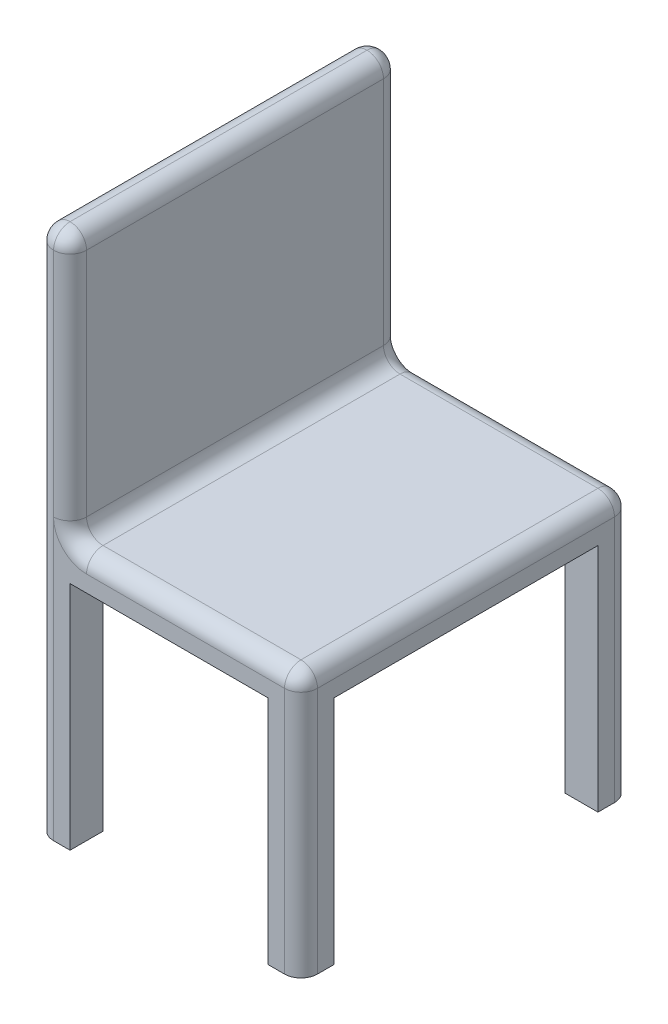
SolidWorks part; units mm, degrees
ref_plane "前基準面" through (0, 0, 0) normal (0, 0, 1) x (1, 0, 0)
ref_plane "上基準面" through (0, 0, 0) normal (0, 1, 0) x (1, 0, 0)
ref_plane "右基準面" through (0, 0, 0) normal (1, 0, 0) x (0, 0, -1)
sketch "草圖1" plane through (0, 0, 0) normal (0, 0, 1) x (1, 0, 0)
  line L0 (0, 0) -> (0, 16)
  line L1 (0, 16) -> (1, 16)
  line L2 (1, 16) -> (1, 8)
  line L3 (1, 8) -> (8, 8)
  line L4 (8, 8) -> (8, 0)
  line L5 (8, 0) -> (7, 0)
  line L6 (7, 0) -> (7, 7)
  line L7 (7, 7) -> (1, 7)
  line L8 (1, 7) -> (1, 0)
  line L9 (1, 0) -> (0, 0)
  point P11 (4.5, 8)
  dimension "D1" = 16
  dimension "D2" = 8
  dimension "D3" = 1
  dimension "D4" = 1
  dimension "D5" = 1
  dimension "D6" = 8
extrude "填料-伸長1" add sketch "草圖1" along normal blind 10
sketch "草圖2" plane through (8, 0, 0) normal (1, 0, 0) x (0, 0, -1)
  line L0 (-10, 0) -> (0, 0) construction
  line L1 (-9, 0) -> (-1, 0)
  line L2 (-9, 0) -> (-9, 7)
  line L3 (-9, 7) -> (-1, 7)
  line L4 (-1, 0) -> (-1, 7)
  line L5 (-10, 0) -> (-10, 8) construction
  line L6 (0, 0) -> (0, 8) construction
  line L7 (-10, 8) -> (0, 8) construction
  dimension "D1" = 1
  dimension "D2" = 1
  dimension "D3" = 1
extrude "除料-伸長1" cut sketch "草圖2" against normal through all
fillet "圓角1" radius 0.5 6 edges at (1, 12, 10) (1, 12, 0) (4.5, 8, 10) (1, 8, 5) (8, 8, 5) (4.5, 8, 0)
fillet "圓角4" radius 0.5 7 edges at (7.8536, 7.8536, 9.8536) (7.8536, 7.8536, 0.1464) (0, 16, 5) (0, 8, 0) (0, 8, 10) (8, 3.75, 10) (8, 3.75, 0)
fillet "圓角5" radius 0.5 5 edges at (0.1464, 15.8536, 9.8536) (0.8536, 16, 9.8536) (1, 16, 5) (0.1464, 15.8536, 0.1464) (0.8536, 16, 0.1464)
